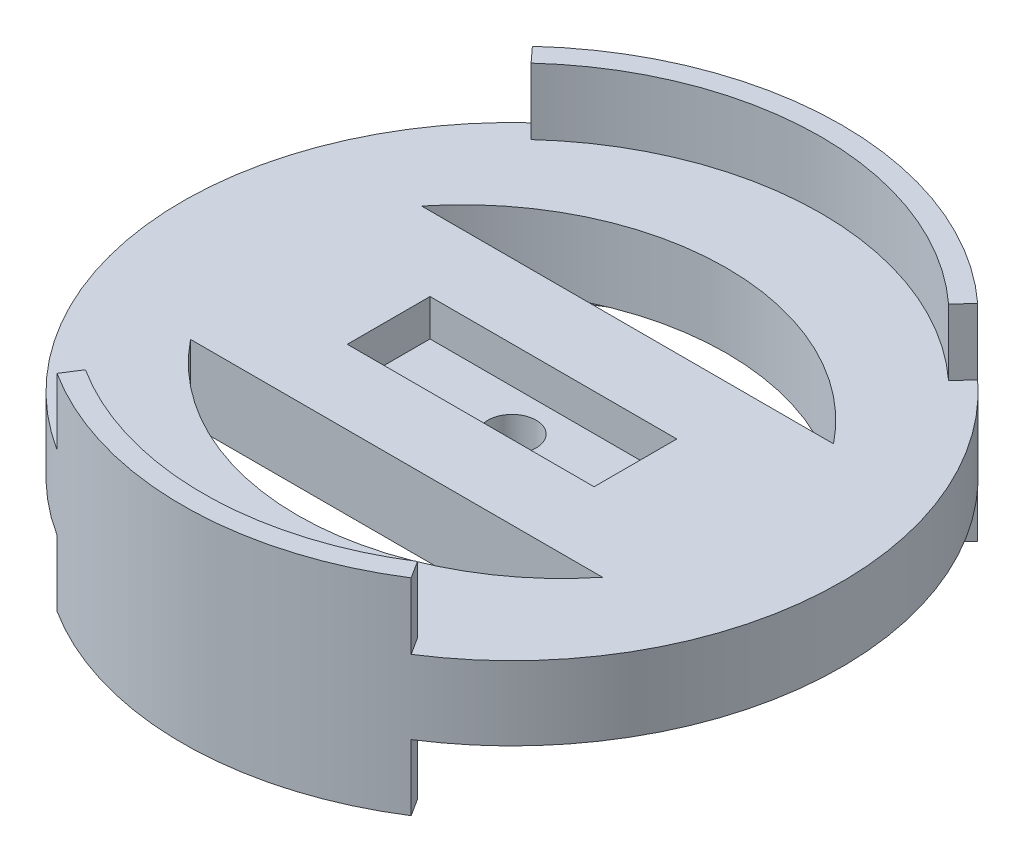
SolidWorks part; units mm, degrees
ref_plane "Front Plane" through (0, 0, 0) normal (0, 0, 1) x (1, 0, 0)
ref_plane "Top Plane" through (0, 0, 0) normal (0, 1, 0) x (1, 0, 0)
ref_plane "Right Plane" through (0, 0, 0) normal (1, 0, 0) x (0, 0, -1)
sketch "Sketch1" plane through (0, 0, 0) normal (0, 1, 0) x (1, 0, 0)
  line L1 (19.0182, -6.3754) -> (-19.0183, -6.3754)
  line L2 (19.0182, -6.3754) -> (19.0182, 6.3754)
  line L3 (19.0182, 6.3754) -> (-19.0183, 6.3754)
  line L4 (-19.0183, -6.3754) -> (-19.0183, 6.3754)
  line L5 (19.0182, -6.3754) -> (-19.0183, 6.3754) construction
  line L6 (19.0182, 6.3754) -> (-19.0183, -6.3754) construction
  circle A0 centre (0, 0) radius 50.8
  circle A1 centre (0, 0) radius 3.7147
  dimension "D1" = 101.6
  dimension "D4" = 7.4295
  dimension "D2" = 38.0365
  dimension "D3" = 12.7508
extrude "Boss-Extrude1" add sketch "Sketch1" along normal blind 5.6642 contours A0 L1 L4 L3 L2 region at (-49.3632, 0, 0)
extrude "Boss-Extrude2" add sketch "Sketch1<3>" against normal blind 5.715 contours A0 L1 L4 L3 L2 | L4 L1 L2 L3 A1 region at (0, 0, 5.9742) region at (-49.3632, 0, 0)
sketch "Sketch1<3>" plane through (0, 0, 0) normal (0, 1, 0) x (1, 0, 0) same geometry as "Sketch1"
sketch "Sketch2" plane through (0, 0, 0) normal (0, 1, 0) x (1, 0, 0)
  line L2 (0, -50.8) -> (0, 50.8) construction
  line L5 (-32.175, 35.1128) -> (-34.32, 37.4537)
  line L7 (32.175, 35.1128) -> (34.32, 37.4537)
  line L9 (-25.5889, -40.1665) -> (-27.2948, -42.8443)
  line L10 (25.5889, -40.1665) -> (27.2948, -42.8443)
  arc A9 (-27.2948, -42.8443) -> (27.2948, -42.8443) centre (0, 0) ccw
  arc A10 (-25.5889, -40.1665) -> (25.5889, -40.1665) centre (0, 0) ccw
  arc A11 (32.175, 35.1128) -> (-32.175, 35.1128) centre (0, 0) ccw
  arc A12 (34.32, 37.4537) -> (-34.32, 37.4537) centre (0, 0) ccw
  point P6 (0, 0)
  point P17 (0, 0)
  point P20 (0, 0)
  dimension "D1" = 101.6
  dimension "D2" = 95.25
  dimension "D3" = 85
  dimension "D4" = 65
  dimension "D5" = 64.35
  dimension "D6" = 51.1778
extrude "Boss-Extrude3" add sketch "Sketch2" along normal mid plane 31.75
sketch "Sketch3" plane through (0, 5.6642, 0) normal (0, 1, 0) x (1, 0, 0)
  line L0 (-31.75, 17.8054) -> (31.75, 17.8054)
  line L1 (0, 0) -> (0, 26.8622) construction
  line L2 (19.0182, 6.3754) -> (-19.0183, 6.3754) construction
  line L3 (19.0183, 0) -> (-19.0183, 0) construction
  line L4 (-19.0183, -6.3754) -> (-19.0183, 6.3754) construction
  line L5 (-31.75, -17.8054) -> (31.75, -17.8054)
  arc A2 (-31.75, 17.8054) -> (31.75, 17.8054) centre (0, -7.6475) cw
  arc A3 (-31.75, -17.8054) -> (31.75, -17.8054) centre (0, 7.6475) ccw
  point P6 (0, 33.0454)
  point P14 (0, 0)
  dimension "D3" = 11.43
  dimension "D2" = 63.5
  dimension "D1" = 15.24
extrude "Cut-Extrude1" cut sketch "Sketch3" against normal through all
